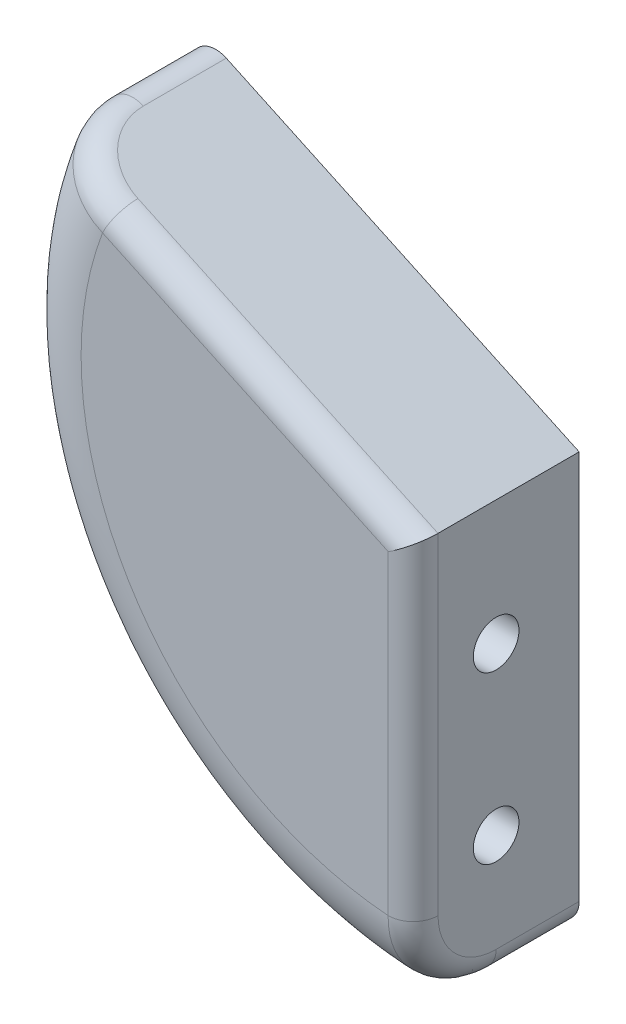
SolidWorks part; units mm, degrees
ref_plane "Front Plane" through (0, 0, 0) normal (0, 0, 1) x (1, 0, 0)
ref_plane "Top Plane" through (0, 0, 0) normal (0, 1, 0) x (1, 0, 0)
ref_plane "Right Plane" through (0, 0, 0) normal (1, 0, 0) x (0, 0, -1)
sketch "Sketch2" plane through (0, 0, 0) normal (0, 0, 1) x (1, 0, 0)
  line L0 (0, 0) -> (-45.3154, 21.1309)
  line L1 (0, 0) -> (0, -50)
  arc A0 (-45.3154, 21.1309) -> (0, -50) centre (0, 0) ccw
  dimension "D1" = 115
  dimension "D3" = 50
extrude "Boss-Extrude1" add sketch "Sketch2" along normal blind 20
sketch "Sketch3" plane through (0, 0, 0) normal (1, 0, 0) x (0, 0, -1)
  line L0 (-20, 0) -> (0, 0) construction
  line L1 (-20, -50) -> (0, -50) construction
  circle A0 centre (-10, -35) radius 2.75
  circle A1 centre (-10, -15) radius 2.75
  point P8 (-10, -50)
  dimension "D2" = 20
  dimension "D3" = 5.5
  dimension "D1" = 35
extrude "Cut-Extrude1" cut sketch "Sketch3" against normal up to next
ref_plane "Plane1" through (-7.5, 0, 0) normal (1, 0, 0) x (0, 0, -1)
sketch "Sketch4" plane through (-7.5, 0, 0) normal (1, 0, 0) x (0, 0, -1)
  circle A0 centre (-10, -15) radius 4.5
  circle A1 centre (-10, -35) radius 4.5
  dimension "D1" = 9
extrude "Cut-Extrude2" cut sketch "Sketch4" against normal up to next
fillet "Fillet1" radius 10 1 edges at (-42.1696, -26.865, 20)
fillet "Fillet2" radius 3 6 edges at (0, -50, 5) (0, -47.0711, 17.0711) (-18.1262, 8.4524, 20) (-42.6609, 19.8931, 17.0711) (0, -20, 20) (-45.3154, 21.1309, 5)
